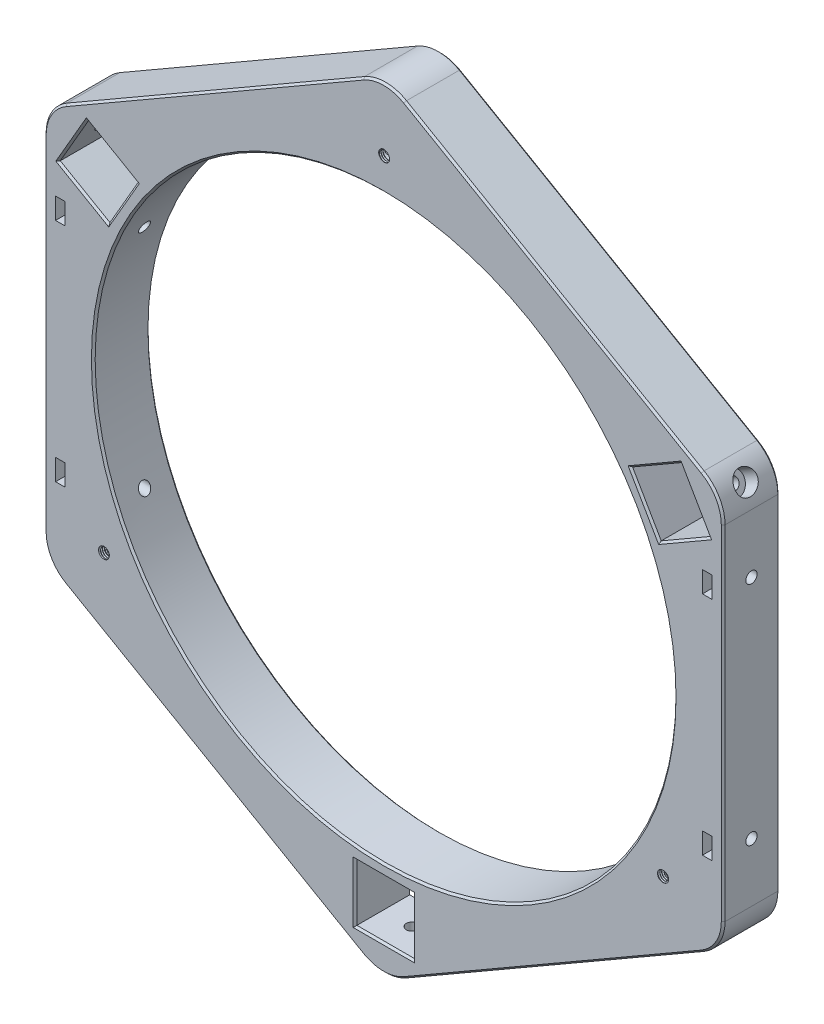
SolidWorks part; units mm, degrees
ref_plane "Top Plane" through (0, 0, 0) normal (0, 0, 1) x (1, 0, 0)
ref_plane "Front Plane" through (0, 0, 0) normal (0, 1, 0) x (1, 0, 0)
ref_plane "Right Plane" through (0, 0, 0) normal (1, 0, 0) x (0, 0, -1)
sketch "Sketch1" plane through (0, 0, 0) normal (0, 0, 1) x (1, 0, 0)
  line L0 (0, 0) -> (0, 121.7219) construction
  line L1 (0, 0) -> (107.9732, 62.3384) construction
  line L2 (0, 0) -> (110.8259, -63.9854) construction
  line L3 (0, 0) -> (0, -117.8434) construction
  line L4 (0, 0) -> (-109.5488, -63.248) construction
  line L5 (0, 0) -> (-114.2494, 65.9619) construction
  line L6 (0, 103.923) -> (90, 51.9615)
  line L7 (90, 51.9615) -> (90, -51.9615)
  line L8 (90, -51.9615) -> (0, -103.923)
  line L9 (0, -103.923) -> (-90, -51.9615)
  line L10 (-90, -51.9615) -> (-90, 51.9615)
  line L11 (-90, 51.9615) -> (0, 103.923)
  circle A0 centre (0, 0) radius 77
  circle A1 centre (0, 0) radius 103.923 construction
  dimension "D1" = 154
  dimension "D4" = 180
  dimension "D2" = 60
  dimension "D3" = 60
extrude "Boss-Extrude1" add sketch "Sketch1" along normal blind 15
sketch "Sketch2" plane through (0, 0, 15) normal (0, 0, 1) x (1, 0, 0)
  line L0 (0, 0) -> (0, -120.5827) construction
  line L1 (-7.6, -80) -> (7.6, -80)
  line L2 (-7.6, -80) -> (-7.6, -95.2)
  line L3 (-7.6, -95.2) -> (7.6, -95.2)
  line L4 (7.6, -80) -> (7.6, -95.2)
  line L5 (-7.6, -80) -> (7.6, -95.2) construction
  line L6 (-7.6, -95.2) -> (7.6, -80) construction
  line L7 (-65.482, 46.5818) -> (-73.082, 33.4182)
  line L8 (-65.482, 46.5818) -> (-78.6456, 54.1818)
  line L9 (-78.6456, 54.1818) -> (-86.2456, 41.0182)
  line L10 (-73.082, 33.4182) -> (-86.2456, 41.0182)
  line L11 (-65.482, 46.5818) -> (-86.2456, 41.0182) construction
  line L12 (-78.6456, 54.1818) -> (-73.082, 33.4182) construction
  line L13 (73.082, 33.4182) -> (65.482, 46.5818)
  line L14 (73.082, 33.4182) -> (86.2456, 41.0182)
  line L15 (86.2456, 41.0182) -> (78.6456, 54.1818)
  line L16 (65.482, 46.5818) -> (78.6456, 54.1818)
  line L17 (73.082, 33.4182) -> (78.6456, 54.1818) construction
  line L18 (86.2456, 41.0182) -> (65.482, 46.5818) construction
  point P0 (0, -87.6)
  point P8 (-75.8638, 43.8)
  point P15 (75.8638, 43.8)
  point P20 (0, 0)
  dimension "D1" = 80
  dimension "D2" = 15.2
  dimension "D3" = 15.2
  dimension "D4" = 3
extrude "Cut-Extrude1" cut sketch "Sketch2" against normal through all
fillet "Fillet1" radius 11.11 6 edges at (-90, -51.9615, 7.5) (-90, 51.9615, 7.5) (0, 103.923, 7.5) (90, 51.9615, 7.5) (90, -51.9615, 7.5) (0, -103.923, 7.5)
sketch "Sketch9" plane through (-82.4456, 47.6, 0) normal (0.866, -0.5, 0) x (0, 0, -1)
  line L0 (0, 0) -> (-36.7336, 0) construction
  line L2 (0, 7.6) -> (0, -7.6) construction
  circle A0 centre (-7.5, 0) radius 1.5
  dimension "D1" = 3
  dimension "D2" = 7.5
extrude "Cut-Extrude6" cut sketch "Sketch9" against normal blind 3
sketch "Sketch10" plane through (-85.0437, 49.1, 0) normal (0.866, -0.5, 0) x (0, 0, -1)
  circle A0 centre (-7.5, 0) radius 3
  dimension "D1" = 6
extrude "Cut-Extrude7" cut sketch "Sketch10" against normal through all
pattern_circular "CirPattern2" count 3 over 360 about axis through (0, 0, 0) along (0, 0, 1) of "Cut-Extrude6", "Cut-Extrude7"
sketch "Sketch11" plane through (0, 0, 15) normal (0, 0, 1) x (1, 0, 0)
  line L0 (0, 0) -> (0, 108.2731) construction
  circle A0 centre (0, 85.5) radius 1.55
  point P11 (0, 0)
  dimension "D1" = 3.1
  dimension "D2" = 85.5
extrude "Cut-Extrude8" cut sketch "Sketch11" against normal blind 10
sketch "Sketch14" plane through (0, 0, 15) normal (0, 0, 1) x (1, 0, 0)
  circle A2 centre (0, 85.5) radius 1.55
  circle A3 centre (0, 85.5) radius 1.55
  dimension "D1" = 0
curve "Helix/Spiral1" pitch 0.5 height 10 turns 20
sketch "Sketch15" plane through (0, 0, 0) normal (1, 0, 0) x (0, 0, -1)
  line L0 (-5, 87.05) -> (-4.65, 87.05)
  line L1 (-5, 87.05) -> (-15, 87.05) construction
  line L2 (-4.65, 87.05) -> (-4.825, 86.7469)
  line L3 (-4.825, 86.7469) -> (-5, 87.05)
  dimension "D1" = 0.35
sweep "Sweep1" add profiles "Sketch15" path "Helix/Spiral1"
pattern_circular "CirPattern3" count 3 over 360 about axis through (0, 0, 15) along (0, 0, -1) of "Cut-Extrude8", "Sweep1"
sketch "Sketch13" plane through (90, 0, 0) normal (1, 0, 0) x (0, 0, -1)
  line L0 (0, 0) -> (-78.4605, 0) construction
  line L1 (-15, -45.5472) -> (-15, 45.5472) construction
  circle A0 centre (-7.5, 30) radius 1.5
  circle A1 centre (-7.5, -30) radius 1.5
  dimension "D1" = 3
  dimension "D2" = 30
  dimension "D3" = 30
  dimension "D4" = 7.5
  dimension "D5" = 7.5
extrude "Cut-Extrude9" cut sketch "Sketch13" against normal through all
sketch "Sketch16" plane through (0, 0, 15) normal (0, 0, 1) x (1, 0, 0)
  line L0 (-93.1471, 30) -> (-78.8508, 30) construction
  line L1 (-87, 32.8) -> (-84.5, 32.8)
  line L2 (-87, 32.8) -> (-87, 27.2)
  line L3 (-87, 27.2) -> (-84.5, 27.2)
  line L4 (-84.5, 32.8) -> (-84.5, 27.2)
  line L5 (-70.262, 31.5) -> (-90, 31.5) construction
  line L6 (-90, 28.5) -> (-71.5315, 28.5) construction
  line L7 (-90, 45.5472) -> (-90, -45.5472) construction
  line L8 (8.3809, 0) -> (-8.3809, 0) construction
  line L9 (-93.1471, -30) -> (-78.8508, -30) construction
  line L10 (-84.5, -32.8) -> (-84.5, -27.2)
  line L11 (-87, -27.2) -> (-84.5, -27.2)
  line L12 (-87, -32.8) -> (-87, -27.2)
  line L13 (-87, -32.8) -> (-84.5, -32.8)
  line L14 (0, -8.3809) -> (0, 8.3809) construction
  line L15 (93.1471, -30) -> (78.8508, -30) construction
  line L16 (93.1471, 30) -> (78.8508, 30) construction
  line L17 (87, -32.8) -> (84.5, -32.8)
  line L18 (87, -32.8) -> (87, -27.2)
  line L19 (87, -27.2) -> (84.5, -27.2)
  line L20 (84.5, -32.8) -> (84.5, -27.2)
  line L21 (84.5, 32.8) -> (84.5, 27.2)
  line L22 (87, 27.2) -> (84.5, 27.2)
  line L23 (87, 32.8) -> (87, 27.2)
  line L24 (87, 32.8) -> (84.5, 32.8)
  dimension "D1" = 5.6
  dimension "D2" = 2.5
  dimension "D3" = 3
extrude "Cut-Extrude10" cut sketch "Sketch16" against normal through all
chamfer "Chamfer3" distance 0.5 angle 45 66 edges at (77, 0, 0) (0, -102.2043, 0) (45, -77.9423, 0) (88.5115, -51.1022, 0) (90, 0, 0) (88.5115, 51.1022, 0) (45, 77.9423, 0) (0, 102.2043, 0) (-45, 77.9423, 0) (-88.5115, 51.1022, 0) (-90, 0, 0) (-88.5115, -51.1022, 0) (-45, -77.9423, 0) (82.4456, 47.6, 0) (79.6638, 37.2182, 0) (69.282, 40, 0) (72.0638, 50.3818, 0) (-82.4456, 47.6, 0) (-72.0638, 50.3818, 0) (-69.282, 40, 0) (-79.6638, 37.2182, 0) (0, -95.2, 0) (-7.6, -87.6, 0) (0, -80, 0) (7.6, -87.6, 0) (77, 0, 15) (-88.5115, 51.1022, 15) (-45, 77.9423, 15) (0, 102.2043, 15) (45, 77.9423, 15) (88.5115, 51.1022, 15) (90, 0, 15) (88.5115, -51.1022, 15) (45, -77.9423, 15) (0, -102.2043, 15) (-45, -77.9423, 15) (-88.5115, -51.1022, 15) (-90, 0, 15) (79.6638, 37.2182, 15) (82.4456, 47.6, 15) (72.0638, 50.3818, 15) (69.282, 40, 15) (-72.0638, 50.3818, 15) (-82.4456, 47.6, 15) (-79.6638, 37.2182, 15) (-69.282, 40, 15) (-7.6, -87.6, 15) (0, -95.2, 15) (7.6, -87.6, 15) (0, -80, 15) (-85.75, 32.8, 0) (-84.5, 30, 0) (-85.75, 27.2, 0) (-87, 30, 0) (-87, -30, 0) (-85.75, -27.2, 0) (-84.5, -30, 0) (-85.75, -32.8, 0) (85.75, -32.8, 0) (84.5, -30, 0) (85.75, -27.2, 0) (87, -30, 0) (87, 30, 0) (85.75, 27.2, 0) (84.5, 30, 0) (85.75, 32.8, 0)
equation "\"H\"=15"
equation "\"D1@Boss-Extrude1\"=\"H\""
equation "\"D2@Sketch9\"=\"H\"/2"
